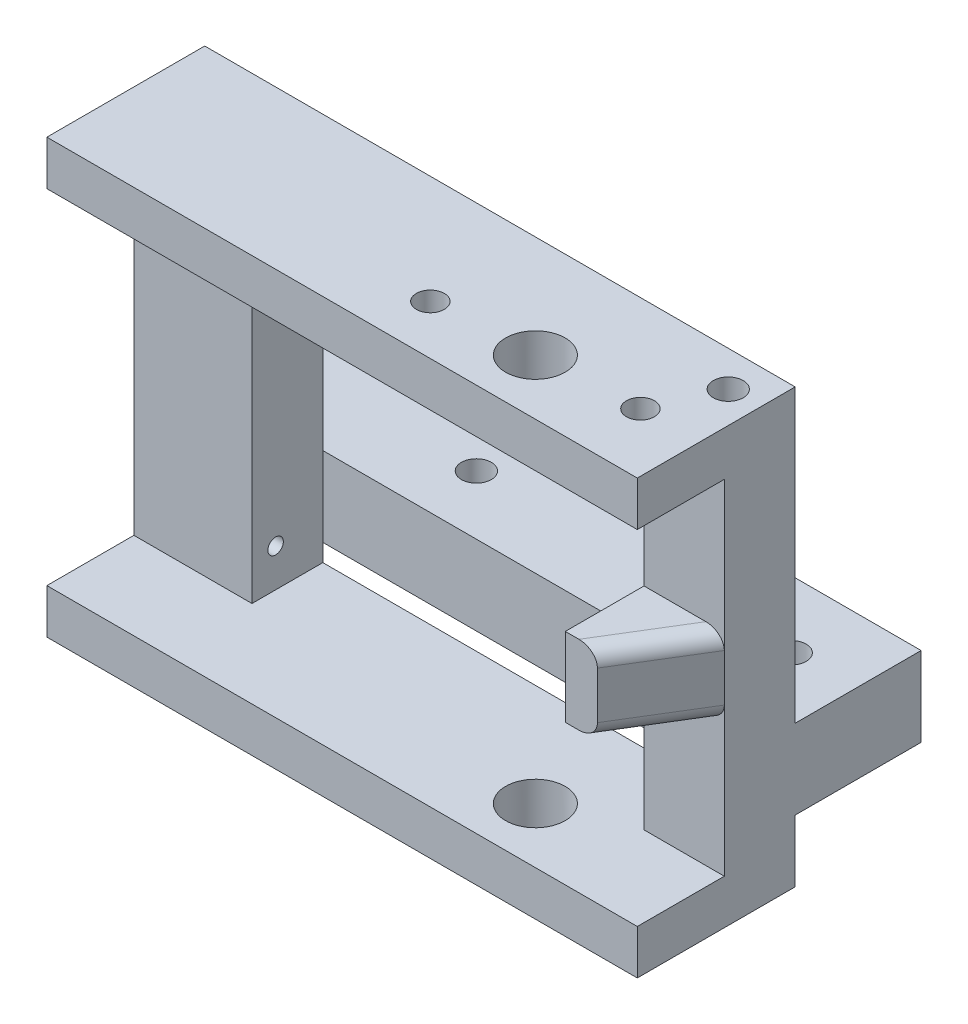
SolidWorks part; units mm, degrees
ref_plane "Front Plane" through (0, 0, 0) normal (0, 0, 1) x (1, 0, 0)
ref_plane "Top Plane" through (0, 0, 0) normal (0, 1, 0) x (1, 0, 0)
ref_plane "Right Plane" through (0, 0, 0) normal (1, 0, 0) x (0, 0, -1)
sketch "Sketch1" plane through (0, 0, 0) normal (0, 0, 1) x (1, 0, 0)
  line L1 (57.15, -34.925) -> (-57.15, -34.925)
  line L2 (57.15, -34.925) -> (57.15, 34.925)
  line L3 (57.15, 34.925) -> (-57.15, 34.925)
  line L4 (-57.15, -34.925) -> (-57.15, 34.925)
  line L5 (57.15, -34.925) -> (-57.15, 34.925) construction
  line L6 (57.15, 34.925) -> (-57.15, -34.925) construction
  point P0 (0, 0)
  dimension "D1" = 69.85
  dimension "D2" = 114.3
extrude "Boss-Extrude1" add sketch "Sketch1" along normal blind 57.15
sketch "Sketch2" plane through (0, 0, 57.15) normal (0, 0, 1) x (1, 0, 0)
  line L0 (-57.15, 34.925) -> (-57.15, -34.925) construction
  line L1 (57.15, -27.725) -> (-57.15, -27.725)
  line L2 (57.15, -27.725) -> (57.15, 27.725)
  line L3 (57.15, 27.725) -> (-57.15, 27.725)
  line L4 (-57.15, -27.725) -> (-57.15, 27.725)
  line L5 (57.15, -27.725) -> (-57.15, 27.725) construction
  line L6 (57.15, 27.725) -> (-57.15, -27.725) construction
  line L7 (57.15, 34.925) -> (-57.15, 34.925) construction
  point P0 (0, 0)
  dimension "D1" = 7.2
extrude "Cut-Extrude2" cut sketch "Sketch2" against normal blind 25.4
sketch "Sketch3" plane through (0, 0, 0) normal (0, 0, -1) x (-1, 0, 0)
  line L0 (-57.15, -34.925) -> (-57.15, 34.925) construction
  line L1 (57.15, 34.925) -> (-57.15, 34.925)
  line L2 (57.15, 34.925) -> (57.15, -12.065)
  line L3 (57.15, -12.065) -> (-57.15, -12.065)
  line L4 (-57.15, 34.925) -> (-57.15, -12.065)
  dimension "D1" = 46.99
extrude "Cut-Extrude3" cut sketch "Sketch3" against normal blind 20.32
sketch "Sketch5" plane through (0, -34.925, 0) normal (0, -1, 0) x (1, 0, 0)
  line L0 (-3.81, 10.79) -> (46.99, 10.79) construction
  line L1 (57.15, 20.32) -> (-57.15, 20.32) construction
  line L2 (57.15, 57.15) -> (57.15, 0) construction
  circle A0 centre (-3.81, 10.79) radius 2.415
  circle A1 centre (46.99, 10.79) radius 2.415
  dimension "D3" = 4.83
  dimension "D4" = 10.16
  dimension "D1" = 9.53
  dimension "D2" = 50.8
sketch "Sketch7" plane through (0, -34.925, 0) normal (0, -1, 0) x (1, 0, 0)
  line L0 (57.15, 57.15) -> (57.15, 0) construction
  line L2 (-57.15, 31.75) -> (57.15, 31.75) construction
  circle A0 centre (31.75, 36.83) radius 4.8
  dimension "D1" = 9.6
  dimension "D2" = 25.4
  dimension "D3" = 5.08
extrude "Cut-Extrude6" cut sketch "Sketch7" against normal up to surface (69.85 mm away) up to face at (0, 34.925, 38.735)
sketch "Sketch8" plane through (0, 34.925, 0) normal (0, 1, 0) x (1, 0, 0)
  line L0 (15.7798, -37.8068) -> (47.7202, -35.8532) construction
  line L1 (57.15, -31.75) -> (-57.15, -31.75) construction
  circle A0 centre (31.75, -36.83) radius 16 construction
  circle A1 centre (15.7798, -37.8068) radius 2.25
  circle A2 centre (47.7202, -35.8532) radius 2.25
  dimension "D1" = 32
  dimension "D2" = 4.5
  dimension "D3" = 3.5
sketch "Sketch9" plane through (0, 0, 31.75) normal (0, 0, 1) x (1, 0, 0)
  line L0 (57.15, 34.925) -> (-57.15, 34.925) construction
  line L5 (57.15, 27.725) -> (-57.15, 27.725) construction
  line L6 (-19.05, 27.725) -> (44.196, 27.725)
  line L7 (-19.05, 27.725) -> (-19.05, -27.725)
  line L8 (-19.05, -27.725) -> (44.196, -27.725)
  line L9 (44.196, 27.725) -> (44.196, -27.725)
  line L10 (-57.15, -27.725) -> (57.15, -27.725) construction
  line L11 (-57.15, 27.725) -> (-57.15, -27.725) construction
  line L12 (57.15, -27.725) -> (57.15, 27.725) construction
  line L13 (-57.15, -34.925) -> (-38.1, -34.925)
  line L14 (-57.15, -34.925) -> (-57.15, 34.925)
  line L15 (-57.15, 34.925) -> (-38.1, 34.925)
  line L16 (-38.1, -34.925) -> (-38.1, 34.925)
  line L17 (-57.15, -34.925) -> (-38.1, 34.925) construction
  line L18 (-57.15, 34.925) -> (-38.1, -34.925) construction
  line L19 (-57.15, -34.925) -> (57.15, -34.925) construction
  point P5 (-47.625, 0)
  dimension "D1" = 12.954
  dimension "25in" = 38.1
  dimension "D2" = 19.05
extrude "Cut-Extrude7" cut sketch "Sketch9" against normal through all both and the other way through all
extrude "Cut-Extrude8" cut sketch "Sketch8" against normal up to next
sketch "Sketch10" [suppressed] plane through (0, 0, 29.21) normal (0, 0, 1) x (1, 0, 0)
  line L1 (-30.607, -1.778) -> (-30.607, -6.604) construction
  circle A0 centre (-33.2489, -4.191) radius 2.286
  point P5 (-30.607, -4.191)
  dimension "D1" = 4.572
sketch "Sketch11" [suppressed] plane through (0, 0, 20.32) normal (0, 0, -1) x (-1, 0, 0)
  circle A0 centre (33.2489, -4.191) radius 2.286
  dimension "D1" = 4.572
extrude "Cut-Extrude9" [suppressed] cut sketch "Sketch11" against normal blind 3.81
sketch "Sketch12" plane through (-19.05, 0, 0) normal (1, 0, 0) x (0, 0, -1)
  line L0 (-31.75, -27.725) -> (-31.75, 27.725) construction
  line L1 (-27.94, -21.59) -> (-27.94, 21.59) construction
  line L2 (-20.32, 27.725) -> (-20.32, -12.065) construction
  circle A0 centre (-27.94, -21.59) radius 1.25
  circle A1 centre (-27.94, 21.59) radius 1.25
  point P0 (-31.75, 0)
  point P8 (-27.94, 0)
  dimension "D1" = 2.5
  dimension "D2" = 7.62
  dimension "D3" = 43.18
extrude "Cut-Extrude10" cut sketch "Sketch12" against normal up to surface (19.05 mm away) up to face at (-38.1, -2.413, 33.274)
sketch "Sketch13" plane through (0, 34.925, 0) normal (0, 1, 0) x (1, 0, 0)
  line L0 (-38.1, -45.7884) -> (57.15, -45.7884)
  line L2 (57.15, -57.15) -> (-38.1, -57.15) construction
  line L3 (47.7202, -35.8532) -> (15.7798, -37.8068) construction
  line L4 (-38.1, -45.7884) -> (-38.1, -57.15)
  line L5 (-38.1, -57.15) -> (57.15, -57.15)
  line L6 (-38.1, -20.32) -> (-38.1, -57.15) construction
  line L7 (57.15, -57.15) -> (57.15, -20.32) construction
  line L8 (57.15, -45.7884) -> (57.15, -57.15)
extrude "Cut-Extrude12" cut sketch "Sketch13" against normal through all
sketch "Sketch14" plane through (44.196, 0, 0) normal (-1, 0, 0) x (0, 0, 1)
  line L0 (0, -27.725) -> (31.75, -27.725) construction
  line L1 (20.32, -12.065) -> (0, -12.065)
  line L2 (20.32, -12.065) -> (20.32, -27.725)
  line L3 (20.32, -27.725) -> (0, -27.725)
  line L4 (0, -12.065) -> (0, -27.725)
extrude "Boss-Extrude2" add sketch "Sketch14" along normal up to next
sketch "Sketch16" plane through (0, 0, 31.75) normal (0, 0, 1) x (1, 0, 0)
  line L0 (44.196, -27.725) -> (44.196, 27.725) construction
  line L1 (57.15, -6.35) -> (44.196, -6.35)
  line L2 (57.15, -6.35) -> (57.15, 6.35)
  line L3 (57.15, 6.35) -> (44.196, 6.35)
  line L4 (44.196, -6.35) -> (44.196, 6.35)
  line L5 (57.15, -6.35) -> (44.196, 6.35) construction
  line L6 (57.15, 6.35) -> (44.196, -6.35) construction
  line L7 (57.15, 6.35) -> (57.15, -6.35) construction
  line L9 (57.15, -27.725) -> (57.15, 27.725) construction
  point P0 (50.673, 0)
  point P7 (57.15, 0)
  dimension "D1" = 12.7
extrude "Boss-Extrude3" add sketch "Sketch16" along normal blind 12.7
sketch "Sketch17" plane through (0, 6.35, 0) normal (0, 1, 0) x (1, 0, 0)
  line L0 (49.375, -44.45) -> (57.15, -31.75)
  line L1 (57.15, -44.45) -> (57.15, -31.75) construction
  line L2 (57.15, -31.75) -> (44.196, -31.75) construction
  line L3 (57.15, -31.75) -> (57.15, -44.45)
  line L4 (57.15, -44.45) -> (49.375, -44.45)
  line L5 (57.15, -44.45) -> (44.196, -44.45) construction
extrude "Cut-Extrude14" cut sketch "Sketch17" against normal blind 12.7
fillet "Fillet4" radius 2.54 2 edges at (53.2625, -6.35, 38.1) (53.2625, 6.35, 38.1)
sketch "Sketch18" plane through (-38.1, 0, 0) normal (-1, 0, 0) x (0, 0, 1)
  line L0 (0, -34.925) -> (45.7884, -34.925) construction
  line L1 (20.32, -35.0627) -> (20.32, -24.9001)
  line L2 (20.32, -24.9001) -> (0, -24.9001)
  line L3 (0, -34.925) -> (0, -12.065) construction
  line L4 (0, -24.9001) -> (0, -34.925)
  line L5 (20.32, -34.925) -> (0, -34.925)
  point P0 (20.32, -34.925)
  point P1 (7.9478, 3.6724)
  line M3 (0, -34.925) -> (45.7884, -34.925)
  line M12 (0, -12.065) -> (0, -34.925)
sketch "Sketch19" plane through (-38.1, 0, 0) normal (-1, 0, 0) x (0, 0, 1)
  line L0 (20.32, -34.925) -> (0, -34.925)
sketch "Sketch20" plane through (-38.1, 0, 0) normal (-1, 0, 0) x (0, 0, 1)
  line L0 (0, -34.925) -> (45.7884, -34.925) construction
  line L1 (20.066, -34.925) -> (20.066, -24.765)
  line L2 (20.066, -24.765) -> (0, -24.765)
  line L3 (0, -34.925) -> (0, -12.065) construction
  line L4 (0, -24.765) -> (0, -34.925)
  line L5 (20.066, -34.925) -> (-0.1509, -34.925)
  point P0 (20.32, -34.925)
  dimension "D1" = 10.16
  dimension "D2" = 20.066
extrude "Cut-Extrude20" cut sketch "Sketch5" against normal through all contours A0 | A1
sketch "Sketch21" plane through (-38.1, 0, 0) normal (-1, 0, 0) x (0, 0, 1)
sketch "Sketch22" plane through (-38.1, 0, 0) normal (-1, 0, 0) x (0, 0, 1)
extrude "Cut-Extrude21" cut sketch "Sketch18" against normal through all contours L1 L2 M12 M3 region at (-38.1, -29.9125, 10.16)
sketch "Sketch23" plane through (0, -34.925, 0) normal (0, -1, 0) x (1, 0, 0)
  line L0 (57.15, 20.32) -> (57.15, 31.75)
  line L1 (57.15, 45.7884) -> (57.15, 20.32) construction
  circle A0 centre (52.07, 26.035) radius 2.413
  point P7 (57.15, 26.035)
  dimension "D2" = 4.826
  dimension "D1" = 11.43
  dimension "D3" = 5.08
extrude "Cut-Extrude22" cut sketch "Sketch23" against normal through all contours A0
